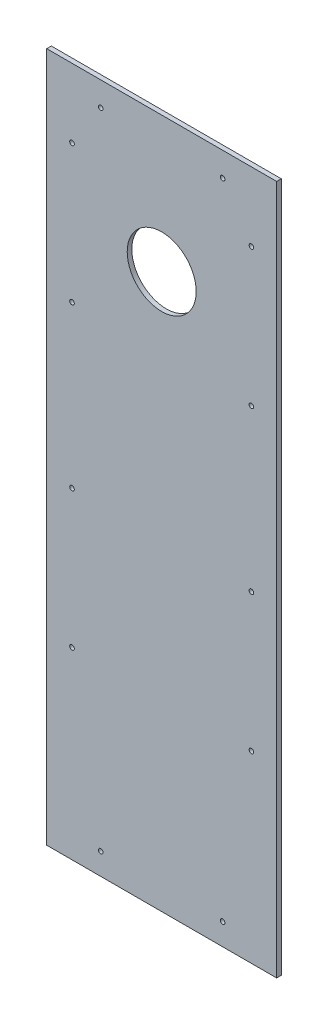
SolidWorks part; units mm, degrees
material "Alumina"
ref_plane "Front Plane" through (0, 0, 0) normal (0, 0, 1) x (1, 0, 0)
ref_plane "Top Plane" through (0, 0, 0) normal (0, 1, 0) x (1, 0, 0)
ref_plane "Right Plane" through (0, 0, 0) normal (1, 0, 0) x (0, 0, -1)
sketch "Sketch1" plane through (0, 0, 0) normal (0, 0, 1) x (1, 0, 0)
  line L1 (50, -150) -> (-50, -150)
  line L2 (50, -150) -> (50, 150)
  line L3 (50, 150) -> (-50, 150)
  line L4 (-50, -150) -> (-50, 150)
  line L5 (50, -150) -> (-50, 150) construction
  line L6 (50, 150) -> (-50, -150) construction
  point P0 (0, 0)
  dimension "D1" = 100
  dimension "D2" = 300
extrude "Boss-Extrude1" add sketch "Sketch1" along normal blind 2
sketch "Sketch2" plane through (0, 0, 2) normal (0, 0, 1) x (1, 0, 0)
  line L0 (-50, 150) -> (-50, -150) construction
  line L1 (50, 150) -> (-50, 150) construction
  line L2 (-50, -150) -> (50, -150) construction
  line L3 (-39, 150) -> (-39, -150) construction
  line L5 (0, -1.1) -> (0, 1.1) construction
  circle A0 centre (-39, 120) radius 1
  circle A4 centre (-39, -70) radius 1
  circle A18 centre (-39, -10) radius 1
  circle A19 centre (-39, 60) radius 1
  circle A20 centre (39, -70) radius 1
  circle A21 centre (39, -10) radius 1
  circle A22 centre (39, 60) radius 1
  circle A23 centre (39, 120) radius 1
  point P7 (-39, -150)
  point P28 (-39, -118.1129)
  point P29 (-39, -118.9614)
  point P30 (0, 0)
  point P32 (-39, -119.4322)
  point P33 (0, 0)
  dimension "D1" = 2
  dimension "D3" = 30
  dimension "D4" = 11
  dimension "D6" = 2
  dimension "D10" = 60
  dimension "D5" = 2
  dimension "D7" = 2
  dimension "D9" = 70
  dimension "D2" = 11
  dimension "D8" = 60
extrude "Cut-Extrude1" cut sketch "Sketch2" against normal blind 10
sketch "Sketch3" plane through (0, 0, 0) normal (0, 0, -1) x (-1, 0, 0)
  line L0 (-50, 150) -> (50, 150) construction
  line L1 (-50, -150) -> (-50, 150) construction
  circle A0 centre (0, 91) radius 15
  dimension "D2" = 30
  dimension "D3" = 50
  dimension "D1" = 59
extrude "Cut-Extrude2" cut sketch "Sketch3" against normal blind 10
sketch "Sketch4" plane through (0, 0, 0) normal (0, 0, -1) x (-1, 0, 0)
  line L0 (-26.5, -140.5) -> (26.5, -140.5) construction
  line L1 (26.5, -140.5) -> (26.5, 139.5) construction
  line L2 (26.5, 139.5) -> (-26.5, 139.5) construction
  line L3 (-26.5, 139.5) -> (-26.5, -140.5) construction
  line L4 (50, -150) -> (-50, -150) construction
  line L5 (-50, 150) -> (50, 150) construction
  line L6 (-50, -150) -> (-50, 150) construction
  line L7 (50, 150) -> (50, -150) construction
  circle A0 centre (-26.5, 139.5) radius 1
  circle A1 centre (26.5, 139.5) radius 1
  circle A2 centre (-26.5, -140.5) radius 1
  circle A3 centre (26.5, -140.5) radius 1
  dimension "D5" = 2
  dimension "D6" = 2
  dimension "D7" = 2
  dimension "D8" = 2
  dimension "D1" = 9.5
  dimension "D2" = 10.5
  dimension "D3" = 23.5
  dimension "D4" = 23.5
extrude "Cut-Extrude3" cut sketch "Sketch4" against normal blind 10
